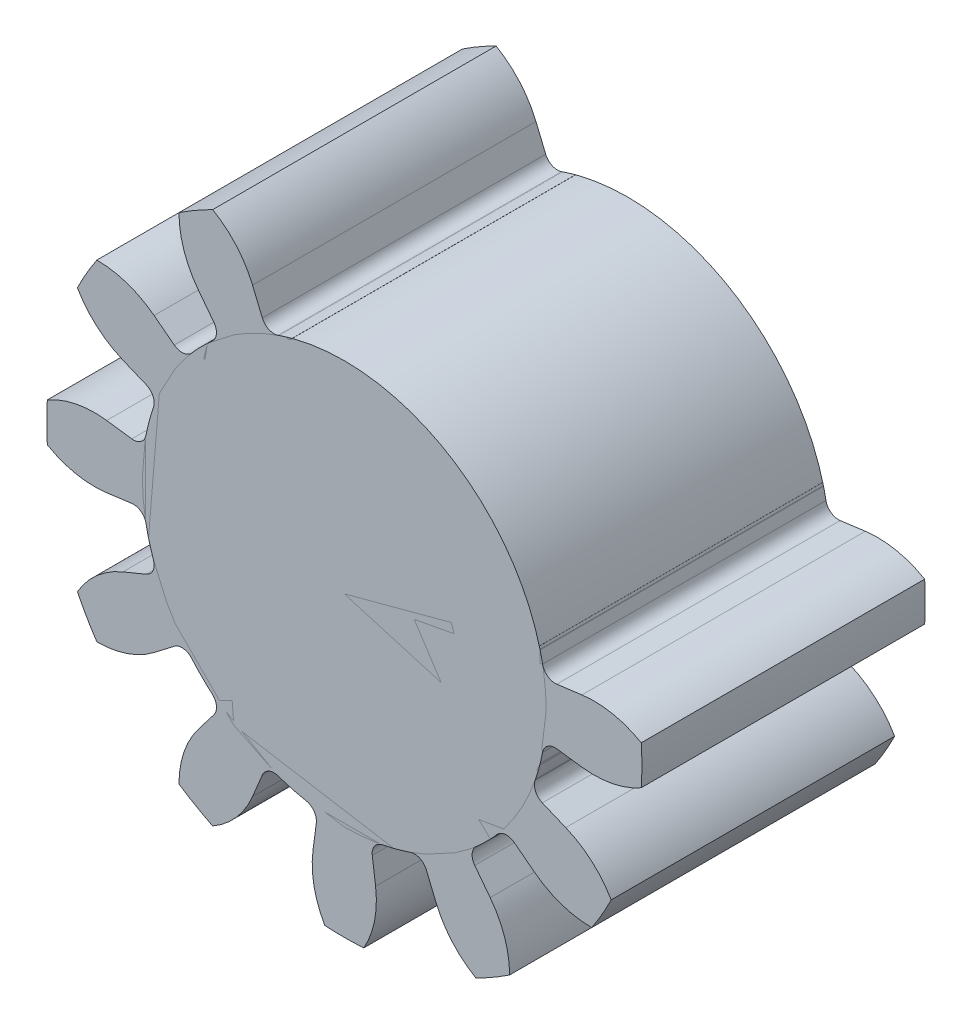
SolidWorks part; units mm, degrees
ref_plane "Front Plane" through (0, 0, 0) normal (0, 0, 1) x (1, 0, 0)
ref_plane "Top Plane" through (0, 0, 0) normal (0, 1, 0) x (1, 0, 0)
ref_plane "Right Plane" through (0, 0, 0) normal (1, 0, 0) x (0, 0, -1)
sketch "Esquisse1" plane through (0, 0, 0) normal (0, 0, 1) x (1, 0, 0)
  line L0 (0, 0) -> (22.1157, 0) construction
  line L1 (0, 0) -> (24.1492, 6.4708) construction
  line L2 (0, 0) -> (24.1492, -6.4708) construction
  line L3 (0, 0) -> (24.9429, 3.2838) construction
  line L4 (0, 0) -> (6.8822, 1.8441)
  line L5 (0, 0) -> (19.7164, -2.5957) construction
  line L6 (0, 0) -> (6.8822, -1.8441)
  line L7 (0, 0) -> (17.7915, 1.1661) construction
  line L8 (7.064, 0.93) -> (8.3849, 1.1039)
  line L9 (7.064, -0.93) -> (8.3849, -1.1039)
  line L10 (0, 0) -> (17.695, -1.1598) construction
  circle A0 centre (0, 0) radius 9 construction
  circle A1 centre (0, 0) radius 10.5 construction
  circle A2 centre (0, 0) radius 7.125 construction
  circle A3 centre (0, 0) radius 8.4572 construction
  arc A4 (6.8822, 1.8441) -> (7.064, 0.93) centre (0, 0) cw
  arc A5 (6.8822, -1.8441) -> (7.064, -0.93) centre (0, 0) ccw
  arc A6 (8.3849, 1.1039) -> (10.4775, 0.6867) centre (8.8176, -2.1828) cw
  arc A7 (10.4775, 0.6867) -> (10.4775, -0.6867) centre (0, 0) cw
  arc A8 (8.3849, -1.1039) -> (10.4775, -0.6867) centre (8.8176, 2.1828) ccw
  dimension "PrimitiveDiameter" = 18
  dimension "OutsideDiameter" = 21
  dimension "InternalDiameter" = 14.25
  dimension "BaseDiameter" = 16.9145
  dimension "DemiToothAngle" = 15
  dimension "QuartToothAngle" = 7.5
  dimension "D1" = 7.5
  dimension "D2" = 3.75
  dimension "D3" = 3.75
extrude "MainGear" add sketch "Esquisse1" along normal blind 10
fillet "Congé1" radius 0.45 2 edges at (7.064, -0.93, 5) (7.064, 0.93, 5)
ref_axis "Axe1" through (0, 0, 10) along (0, 0, -1)
pattern_circular "Répétition circulaire1" count 9 every 30 about axis through (0, 0, 10) along (0, 0, -1) of "MainGear", "Congé1"
sketch "Esquisse3" plane through (0, 0, 0) normal (0, 0, 1) x (1, 0, 0)
  circle A0 centre (0, 0) radius 3.1
  dimension "D1" = 6.2
sketch "Esquisse5" plane through (0, 0, 10) normal (0, 0, 1) x (1, 0, 0)
  circle A0 centre (0, 0) radius 7.125
extrude "MainBaseCircle" add sketch "Esquisse5" against normal through all
sketch "Esquisse9" [suppressed] plane through (0, 0, 10) normal (0, 0, 1) x (1, 0, 0)
  circle A0 centre (0, 0) radius 7.125
  circle A1 centre (0, 0) radius 7.125 construction
  circle A2 centre (0, 0) radius 3.1
  dimension "D1" = 6.2
extrude "GearBottomFix" [suppressed] add sketch "Esquisse9" along normal blind 2
extrude "GearHole" [suppressed] cut sketch "Esquisse3" along normal through all
equation "\"Modulo\"= 1.5mm"
equation "\"ToothCount\"= 12"
equation "\"PrimitiveDiameter@Esquisse1\"= \"Modulo\" * \"ToothCount\""
equation "\"OutsideDiameter@Esquisse1\" = \"Modulo\" *  ( \"ToothCount\" + 2 ) "
equation "\"Angle\"= 20deg"
equation "\"BaseDiameter@Esquisse1\" = \"PrimitiveDiameter@Esquisse1\" * cos ( \"Angle\" ) "
equation "\"DemiToothAngle@Esquisse1\" = 180 / \"ToothCount\""
equation "\"QuartToothAngle@Esquisse1\"= \"DemiToothAngle@Esquisse1\" / 2"
equation "\"D1@Esquisse1\"= \"QuartToothAngle@Esquisse1\""
equation "\"D2@Esquisse1\"= \"QuartToothAngle@Esquisse1\" / 2"
equation "\"D3@Esquisse1\"= \"D2@Esquisse1\""
equation "\"D2@Répétition circulaire1\"=360/\"ToothCount\""
equation "\"D1@Congé1\"=\"Modulo\"*0.3"
